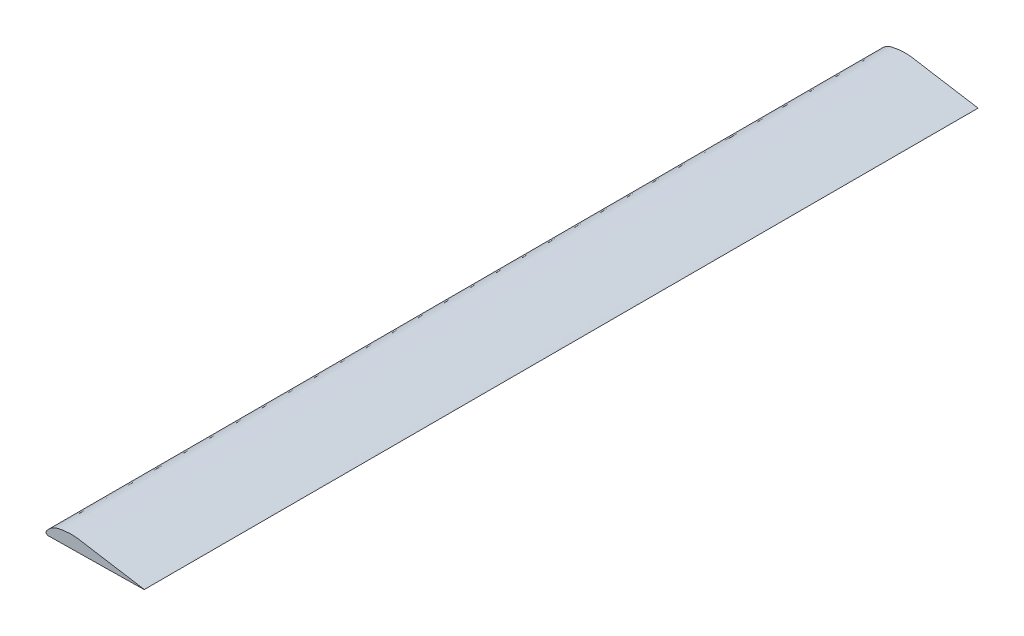
SolidWorks part; units mm, degrees
ref_plane "Front Plane" through (0, 0, 0) normal (0, 0, 1) x (1, 0, 0)
ref_plane "Top Plane" through (0, 0, 0) normal (0, 1, 0) x (1, 0, 0)
ref_plane "Right Plane" through (0, 0, 0) normal (1, 0, 0) x (0, 0, -1)
curve "Curve1"
  spline degree 3 poles (23.3936, -0.0091, 0) (26.5421, -0.0724, 0) (22.846, 0.3911, 0) (21.1467, 0.7182, 0) (18.8415, 1.0905, 0) (16.6987, 1.4511, 0) (14.5123, 1.8136, 0) (12.3379, 2.1801, 0) (10.0402, 2.548, 0) (7.9315, 2.9561, 0) (5.877, 2.9795, 0) (4.0472, 2.7683, 0) (2.4121, 2.4386, 0) (1.3547, 1.792, 0) (0.8323, 1.347, 0) (0.4716, 0.9793, 0) (0.1356, 0.6323, 0) (-0.1448, 0.0575, 0) (0.2731, -0.3048, 0) (1.1151, -0.4813, 0) (2.4547, -0.3119, 0) (4.2154, -0.3378, 0) (5.982, -0.2963, 0) (7.7469, -0.2729, 0) (9.5123, -0.2447, 0) (11.2776, -0.2178, 0) (13.0428, -0.1905, 0) (14.8085, -0.1633, 0) (16.5723, -0.136, 0) (18.3434, -0.1092, 0) (20.0868, -0.0803, 0) (21.934, -0.0593, 0) (23.3936, -0.0091, 0) (26.5421, -0.0724, 0) (22.846, 0.3911, 0) knots -0.101253 -0.067502 -0.033751 0 0.042194 0.084388 0.126583 0.168777 0.210971 0.253165 0.295359 0.344459 0.376025 0.412649 0.450339 0.470158 0.482904 0.489771 0.499409 0.512015 0.518882 0.527487 0.561238 0.594988 0.628739 0.66249 0.696241 0.729992 0.763743 0.797494 0.831245 0.864996 0.898747 0.932498 0.966249 1 1.042194 1.084388 1.126583 periodic
sketch "Sketch1" plane through (0, 0, 0) normal (0, 0, 1) x (1, 0, 0)
  line L0 (0, 0) -> (76.2, 0) construction
  line L1 (38.1, 0) -> (38.1, 6.3518) construction
  spline S0 degree 3 poles (23.3936, -0.0091) (26.5421, -0.0724) (22.846, 0.3911) (21.1467, 0.7182) (18.8415, 1.0905) (16.6987, 1.4511) (14.5123, 1.8136) (12.3379, 2.1801) (10.0402, 2.548) (7.9315, 2.9561) (5.877, 2.9795) (4.0472, 2.7683) (2.4121, 2.4386) (1.3547, 1.792) (0.8323, 1.347) (0.4716, 0.9793) (0.1356, 0.6323) (-0.1448, 0.0575) (0.2731, -0.3048) (1.1151, -0.4813) (2.4547, -0.3119) (4.2154, -0.3378) (5.982, -0.2963) (7.7469, -0.2729) (9.5123, -0.2447) (11.2776, -0.2178) (13.0428, -0.1905) (14.8085, -0.1633) (16.5723, -0.136) (18.3434, -0.1092) (20.0868, -0.0803) (21.934, -0.0593) (23.3936, -0.0091) (26.5421, -0.0724) (22.846, 0.3911) knots -0.101253 -0.067502 -0.033751 0 0.042194 0.084388 0.126583 0.168777 0.210971 0.253165 0.295359 0.344459 0.376025 0.412649 0.450339 0.470158 0.482904 0.489771 0.499409 0.512015 0.518882 0.527487 0.561238 0.594988 0.628739 0.66249 0.696241 0.729992 0.763743 0.797494 0.831245 0.864996 0.898747 0.932498 0.966249 1 1.042194 1.084388 1.126583 only from (25.4, 0) to (25.4, 0) construction
  spline S1 degree 3 poles (23.3936, -0.0091) (26.5421, -0.0724) (22.846, 0.3911) (21.1467, 0.7182) (18.8415, 1.0905) (16.6987, 1.4511) (14.5123, 1.8136) (12.3379, 2.1801) (10.0402, 2.548) (7.9315, 2.9561) (5.877, 2.9795) (4.0472, 2.7683) (2.4121, 2.4386) (1.3547, 1.792) (0.8323, 1.347) (0.4716, 0.9793) (0.1356, 0.6323) (-0.1448, 0.0575) (0.2731, -0.3048) (1.1151, -0.4813) (2.4547, -0.3119) (4.2154, -0.3378) (5.982, -0.2963) (7.7469, -0.2729) (9.5123, -0.2447) (11.2776, -0.2178) (13.0428, -0.1905) (14.8085, -0.1633) (16.5723, -0.136) (18.3434, -0.1092) (20.0868, -0.0803) (21.934, -0.0593) (23.3936, -0.0091) (26.5421, -0.0724) (22.846, 0.3911) knots -0.101253 -0.067502 -0.033751 0 0.042194 0.084388 0.126583 0.168777 0.210971 0.253165 0.295359 0.344459 0.376025 0.412649 0.450339 0.470158 0.482904 0.489771 0.499409 0.512015 0.518882 0.527487 0.561238 0.594988 0.628739 0.66249 0.696241 0.729992 0.763743 0.797494 0.831245 0.864996 0.898747 0.932498 0.966249 1 1.042194 1.084388 1.126583 only from (25.4, 0) to (25.4, 0) construction
  spline S2 degree 3 poles (7.0181, -0.0027) (7.9626, -0.0217) (6.8538, 0.1173) (6.344, 0.2154) (5.6525, 0.3272) (5.0096, 0.4353) (4.3537, 0.5441) (3.7014, 0.654) (3.012, 0.7644) (2.3795, 0.8868) (1.7631, 0.8938) (1.2141, 0.8305) (0.7236, 0.7316) (0.4064, 0.5376) (0.2497, 0.4041) (0.1415, 0.2938) (0.0407, 0.1897) (-0.0434, 0.0172) (0.0819, -0.0914) (0.3345, -0.1444) (0.7364, -0.0936) (1.2646, -0.1013) (1.7946, -0.0889) (2.3241, -0.0819) (2.8537, -0.0734) (3.3833, -0.0653) (3.9128, -0.0571) (4.4426, -0.049) (4.9717, -0.0408) (5.503, -0.0328) (6.026, -0.0241) (6.5802, -0.0178) (7.0181, -0.0027) (7.9626, -0.0217) (6.8538, 0.1173) knots -0.101253 -0.067502 -0.033751 0 0.042194 0.084388 0.126583 0.168777 0.210971 0.253165 0.295359 0.344459 0.376025 0.412649 0.450339 0.470158 0.482904 0.489771 0.499409 0.512015 0.518882 0.527487 0.561238 0.594988 0.628739 0.66249 0.696241 0.729992 0.763743 0.797494 0.831245 0.864996 0.898747 0.932498 0.966249 1 1.042194 1.084388 1.126583 only from (7.62, 0) to (7.62, 0) construction
  spline S3 degree 3 poles (70.1808, -0.0274) (79.6263, -0.2171) (68.5381, 1.1733) (63.44, 2.1545) (56.5245, 3.2716) (50.0961, 4.3533) (43.5369, 5.4409) (37.0137, 6.5402) (30.1205, 7.6441) (23.7946, 8.8682) (17.6309, 8.9384) (12.1415, 8.3049) (7.2364, 7.3158) (4.0642, 5.3761) (2.4969, 4.0409) (1.4147, 2.9379) (0.4067, 1.8969) (-0.4343, 0.1725) (0.8192, -0.9145) (3.3454, -1.444) (7.364, -0.9357) (12.6463, -1.0134) (17.9459, -0.889) (23.2408, -0.8188) (28.5369, -0.7341) (33.8329, -0.6533) (39.1284, -0.5714) (44.4256, -0.4899) (49.7168, -0.4079) (55.0303, -0.3276) (60.2604, -0.241) (65.802, -0.1778) (70.1808, -0.0274) (79.6263, -0.2171) (68.5381, 1.1733) knots -0.101253 -0.067502 -0.033751 0 0.042194 0.084388 0.126583 0.168777 0.210971 0.253165 0.295359 0.344459 0.376025 0.412649 0.450339 0.470158 0.482904 0.489771 0.499409 0.512015 0.518882 0.527487 0.561238 0.594988 0.628739 0.66249 0.696241 0.729992 0.763743 0.797494 0.831245 0.864996 0.898747 0.932498 0.966249 1 1.042194 1.084388 1.126583 only from (76.2, 0) to (76.2, 0)
  dimension "D1" = 76.2
  dimension "D2" = 6.3518
extrude "Boss-Extrude1" add sketch "Sketch1" along normal blind 647.7
ref_plane "Plane1" through (0, 0, 323.85) normal (0, 0, 1) x (1, 0, 0)
sketch "Sketch2" plane through (0, 0, 323.85) normal (0, 0, 1) x (1, 0, 0)
  line L0 (0, 0) -> (0, -27.7876) construction
  line L1 (0, -27.7876) -> (7.62, -27.7876) construction
  circle A0 centre (7.62, -27.7876) radius 1.27 construction
  dimension "D3" = 2.54
  dimension "D1" = 27.7876
  dimension "D2" = 7.62
